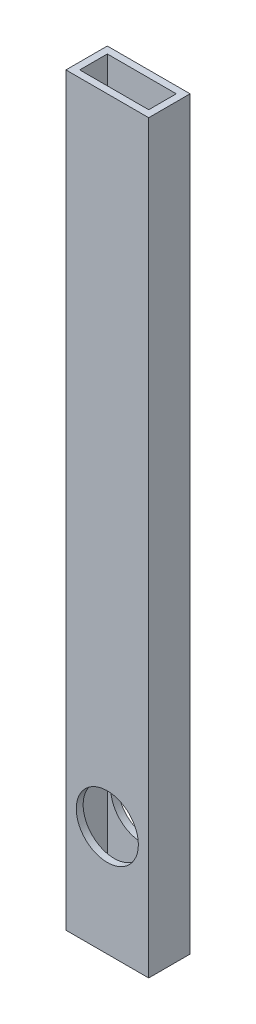
SolidWorks part; units mm, degrees
ref_plane "Front Plane" through (0, 0, 0) normal (0, 0, 1) x (1, 0, 0)
ref_plane "Top Plane" through (0, 0, 0) normal (0, 1, 0) x (1, 0, 0)
ref_plane "Right Plane" through (0, 0, 0) normal (1, 0, 0) x (0, 0, -1)
sketch "Sketch1" plane through (0, 0, 0) normal (0, 1, 0) x (1, 0, 0)
  line L0 (3.175, 15.875) -> (34.925, 15.875)
  line L1 (0, 0) -> (38.1, 0)
  line L2 (0, 0) -> (0, 19.05)
  line L3 (0, 19.05) -> (38.1, 19.05)
  line L4 (38.1, 0) -> (38.1, 19.05)
  line L5 (34.925, 3.175) -> (34.925, 15.875)
  line L6 (3.175, 3.175) -> (34.925, 3.175)
  line L7 (3.175, 3.175) -> (3.175, 15.875)
  dimension "D1" = 38.1
  dimension "D2" = 19.05
extrude "Boss-Extrude1" add sketch "Sketch1" along normal blind 342.9
sketch "Sketch2" plane through (0, 0, 0) normal (0, 0, 1) x (1, 0, 0)
  line L0 (19.05, 0) -> (19.05, 50.8) construction
  line L1 (0, 0) -> (38.1, 0) construction
  circle A0 centre (19.05, 50.8) radius 14.2875
  dimension "D1" = 50.8
extrude "Cut-Extrude1" cut sketch "Sketch2" against normal through all
